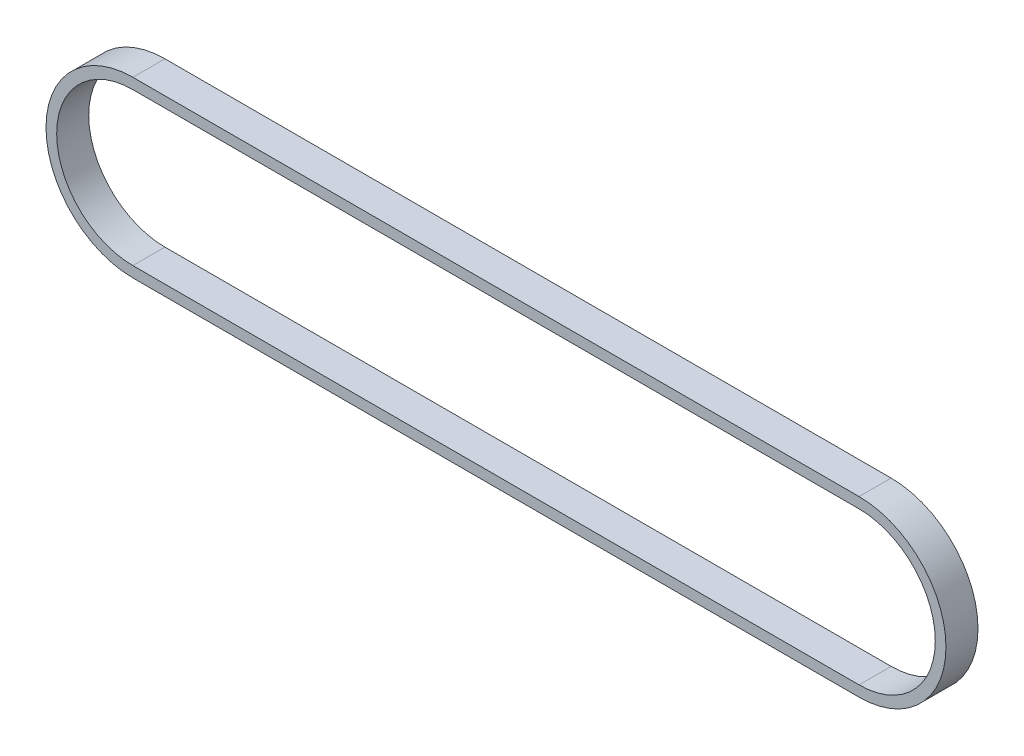
SolidWorks part; units mm, degrees
material "NEOPRENE"
ref_plane "Plano frontal" through (0, 0, 0) normal (0, 0, 1) x (1, 0, 0)
ref_plane "Plano superior" through (0, 0, 0) normal (0, 1, 0) x (1, 0, 0)
ref_plane "Plano direito" through (0, 0, 0) normal (1, 0, 0) x (0, 0, -1)
sketch "Esboço1" plane through (0, 0, 0) normal (0, 0, 1) x (1, 0, 0)
  line L0 (0, 22.9) -> (203.9448, 22.9) construction
  line L1 (0, -22.9) -> (203.9448, -22.9) construction
  line L2 (0, 21.4) -> (203.9448, 21.4)
  line L3 (0, -24.4) -> (203.9448, -24.4)
  line L4 (0, 24.4) -> (203.9448, 24.4)
  line L5 (0, -21.4) -> (203.9448, -21.4)
  circle A0 centre (0, 0) radius 22.9 construction
  circle A1 centre (203.9448, 0) radius 22.9 construction
  circle A2 centre (0, 0) radius 24.4
  circle A3 centre (203.9448, 0) radius 24.4
  circle A4 centre (0, 0) radius 21.4
  circle A5 centre (203.9448, 0) radius 21.4
  dimension "D1" = 45.8
  dimension "D2" = 203.9448
  dimension "D3" = 1.5
  dimension "D4" = 1.5
extrude "Ressalto-extrusão1" add sketch "Esboço1" along normal mid plane 9 contours A4 L2 A2 L5 | A3 L4 A2 L2 | A3 L5 A2 L3 | A5 L5 A3 L2 region at (-22.0071, 0, 0) region at (101.9724, 22.9247, 0) region at (198.0456, 23.0499, 0) region at (101.9724, -22.9247, 0)
